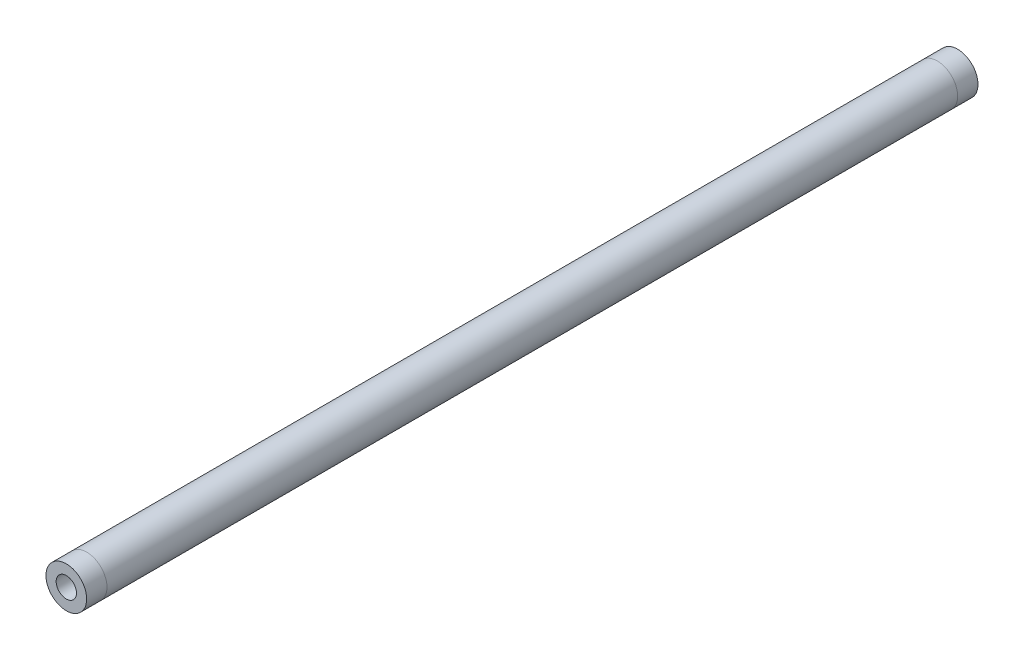
SolidWorks part; units mm, degrees
material "AISI 4130 Steel, normalized at 870C"
ref_plane "Front Plane" through (0, 0, 0) normal (0, 0, 1) x (1, 0, 0)
ref_plane "Top Plane" through (0, 0, 0) normal (0, 1, 0) x (1, 0, 0)
ref_plane "Right Plane" through (0, 0, 0) normal (1, 0, 0) x (0, 0, -1)
sketch "Axis" plane through (0, 0, 0) normal (0, 1, 0) x (1, 0, 0)
  line L0 (0, 0) -> (0, 21.9075) construction
  line L1 (0, 21.9075) -> (0, 300.0818) construction
  line L2 (0, 300.0818) -> (0, 321.9893) construction
  dimension "D1" = 21.9075
  dimension "D2" = 321.9893
sketch "Sketch2" plane through (0, 0, 0) normal (0, 0, 1) x (1, 0, 0)
  circle A0 centre (0, 0) radius 6.35
  circle A1 centre (0, 0) radius 3.175
  circle A2 centre (0, 0) radius 4.7625
  dimension "D1" = 12.7
  dimension "D2" = 6.35
  dimension "D3" = 9.525
extrude "Threaded Insert 1-1" add sketch "Sketch2" against normal blind 6.35 from vertex contours A0 A2 | A2 A1 region at (-6.1704, 0, 0) region at (-4.6278, 0, 0) starting at point (0, 0, -21.9075)
extrude "Threaded Insert 1-2" add sketch "Sketch2<5>" against normal blind 9.525 from surface contours A2 A1 region at (-4.6278, 0, 0) starting at face at (6.35, 0, -28.2575)
sketch "Sketch2<5>" plane through (0, 0, 0) normal (0, 0, 1) x (1, 0, 0) same geometry as "Sketch2"
extrude "Boss-Extrude4" add sketch "Sketch2<7>" along normal blind 6.35 from vertex separate body contours A0 A2 | A2 A1 region at (-6.1704, 0, 0) region at (-4.6278, 0, 0) starting at point (0, 0, -300.0818)
sketch "Sketch2<7>" plane through (0, 0, 0) normal (0, 0, 1) x (1, 0, 0) same geometry as "Sketch2"
extrude "Boss-Extrude5" add sketch "Sketch2<8>" along normal blind 9.525 from surface contours A2 A1 region at (-4.6278, 0, 0) starting at face at (6.35, 0, -293.7318)
sketch "Sketch2<8>" plane through (0, 0, 0) normal (0, 0, 1) x (1, 0, 0) same geometry as "Sketch2"
extrude "Boss-Extrude6" add sketch "Sketch2<9>" against normal up to surface (293.7318 mm away) from surface separate body contours A0 A2 region at (-6.1704, 0, 0) up to face at (6.35, 0, -293.7318) starting at face at (4.7625, 0, -28.2575)
sketch "Sketch2<9>" plane through (0, 0, 0) normal (0, 0, 1) x (1, 0, 0) same geometry as "Sketch2"
move or copy body "Body-Move/Copy1" [suppressed] bodies to move or copy 102 105 106 parameters "D1"=0, "D2"=0, "D3"=0
equation "\"Tube Outer Diameter\"= .5"
equation "\"Tube Inner Diameter\"= .375"
equation "\"Rod end Diameter\"= .25"
equation "\"Threaded Insert Out\"= .25"
equation "\"Threaded Insert In\"= .375'`"
equation "\"D1@Sketch2\"=\"Tube Outer Diameter\""
equation "\"D2@Sketch2\"=\"Rod end Diameter\""
equation "\"D1@Threaded Insert 1-1\" = \"Threaded Insert Out\""
equation "\"D3@Sketch2\"=\"Tube Inner Diameter\""
equation "\"D1@Threaded Insert 1-2\" = \"Threaded Insert In\""
equation "\"D1@Boss-Extrude4\"=\"Threaded Insert Out\""
equation "\"D1@Boss-Extrude5\"=\"Threaded Insert In\""
